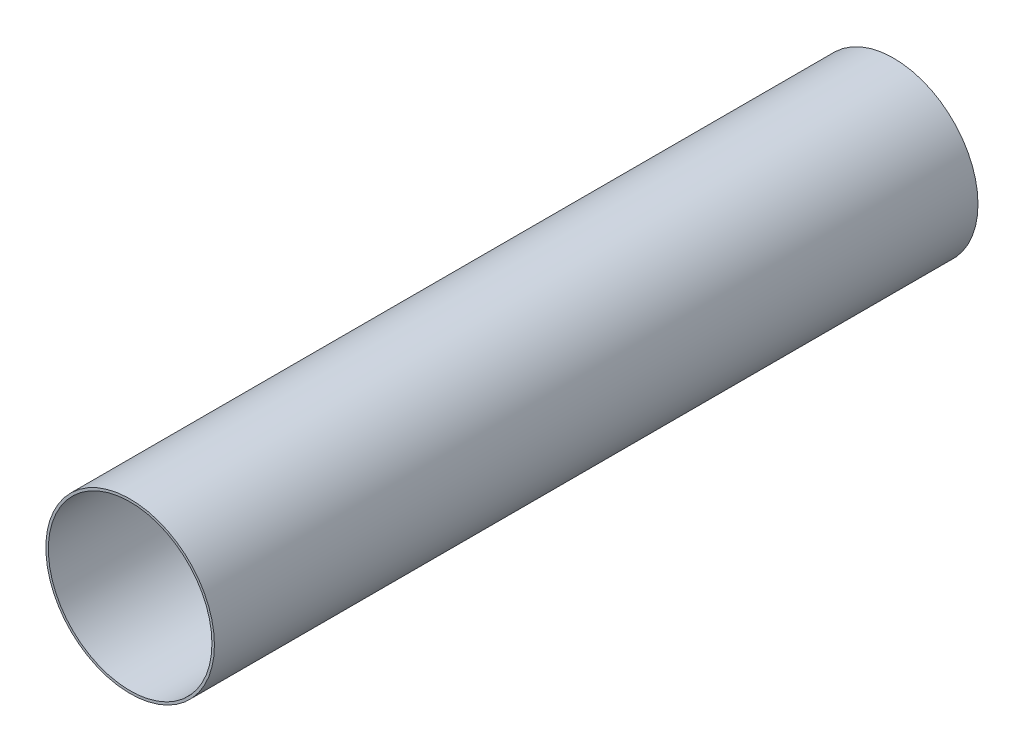
SolidWorks part; units mm, degrees
ref_plane "Front Plane" through (0, 0, 0) normal (0, 0, 1) x (1, 0, 0)
ref_plane "Top Plane" through (0, 0, 0) normal (0, 1, 0) x (1, 0, 0)
ref_plane "Right Plane" through (0, 0, 0) normal (1, 0, 0) x (0, 0, -1)
sketch "Sketch1" plane through (0, 0, 0) normal (0, 0, 1) x (1, 0, 0)
  circle A0 centre (0, 0) radius 39.2557
  circle A1 centre (0, 0) radius 38.1
  dimension "D1" = 76.2
  dimension "D2" = 78.5114
extrude "Boss-Extrude1" add sketch "Sketch1" along normal mid plane 355.6
equation "\"AIRFRAME_OD\"= 3.091in"
equation "\"AIRFRAME_ID\"= 3.00in"
equation "\"FLAT_T\" = 0.125in"
equation "\"NOSE_EXP_L\"= 3.5in"
equation "\"NOSE_SHOULDER_L\" = 5in"
equation "\"MAIN_L\" = 30in"
equation "\"RECO_COUP_L\" = 6in"
equation "\"RECO_SWITCH_L\" = 1.5in"
equation "\"DROGUE_L\" = 14in"
equation "\"ATS_FORE_COUP_L\" = 4in"
equation "\"ATS_AFT_COUP_L\" = 4in"
equation "\"LOWER_L\" = 16in"
equation "\"FIN_N\" = 4"
equation "\"CR_AFT_X\" = 0.5in"
equation "\"CR_FORE_X\" = 6in"
equation "\"D1@Sketch1\"=\"AIRFRAME_ID\""
equation "\"D2@Sketch1\"=\"AIRFRAME_OD\""
equation "\"D1@Boss-Extrude1\"=\"DROGUE_L\""
equation "\"FIN_ROOT\" = 5in"
equation "\"FIN_X\" = 0.75in"
equation "\"MOTOR_OD\" = 2.25in"
equation "\"MOTOR_ID\" = 2.126in"
